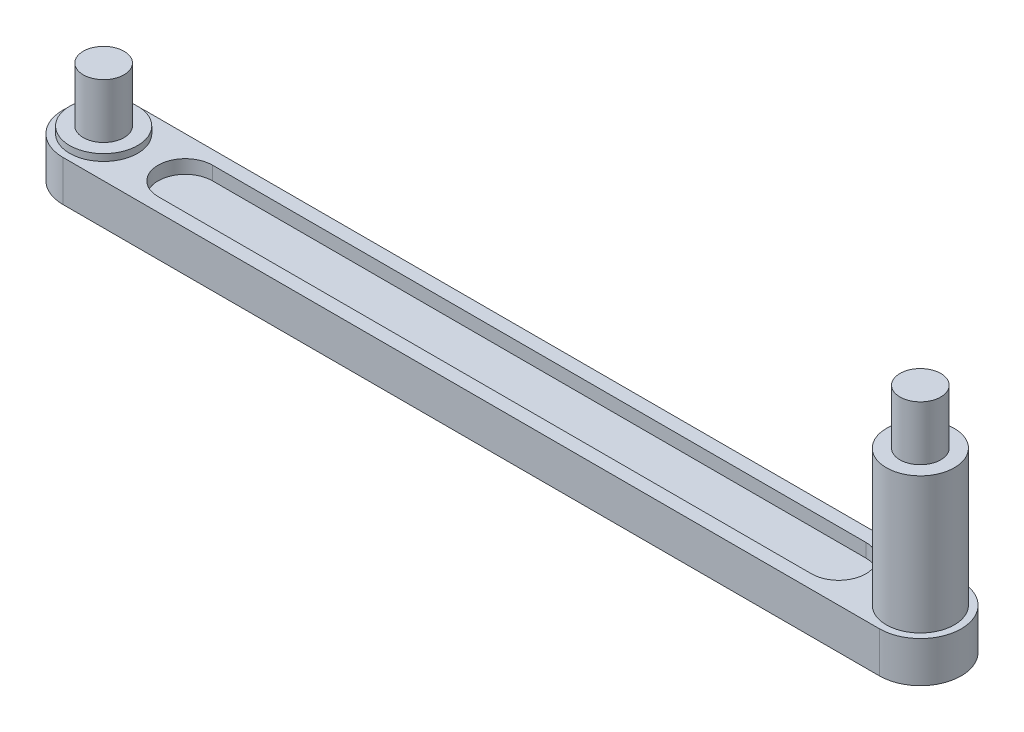
SolidWorks part; units mm, degrees
material "ABS"
ref_plane "Спереди" through (0, 0, 0) normal (0, 0, 1) x (1, 0, 0)
ref_plane "Сверху" through (0, 0, 0) normal (0, 1, 0) x (1, 0, 0)
ref_plane "Справа" through (0, 0, 0) normal (1, 0, 0) x (0, 0, -1)
sketch "Эскиз1" plane through (0, 0, 0) normal (0, 1, 0) x (1, 0, 0)
  line L0 (30, 0) -> (-30, 0) construction
  line L1 (30, -3) -> (-30, -3)
  line L2 (30, 3) -> (-30, 3)
  arc A0 (30, -3) -> (30, 3) centre (30, 0) ccw
  arc A1 (-30, 3) -> (-30, -3) centre (-30, 0) ccw
  circle A2 centre (-30, 0) radius 2.5 construction
  point P2 (0, 0)
  dimension "D2" = 5
  dimension "D3" = 0.5
  dimension "D1" = 60
extrude "Бобышка-Вытянуть1" add sketch "Эскиз1" along normal blind 3
sketch "Эскиз2" plane through (0, 3, 0) normal (0, 1, 0) x (1, 0, 0)
  circle A0 centre (-30, 0) radius 2.5
  circle A1 centre (30, 0) radius 2.5
  arc M1 (30, -3) -> (30, 3) centre (30, 0) ccw
  arc M3 (-30, 3) -> (-30, -3) centre (-30, 0) ccw
extrude "Бобышка-Вытянуть2" add sketch "Эскиз2" along normal blind 0.5 contours A0 M3 region at (-30, 3, 0)
sketch "Эскиз3" plane through (0, 3, 0) normal (0, 1, 0) x (1, 0, 0)
  circle A0 centre (-30, 0) radius 1.5
  circle A1 centre (30, 0) radius 1.5
  dimension "D2" = 3
extrude "Бобышка-Вытянуть3" add sketch "Эскиз3" along normal offset from surface (4.5 mm away) 4 contours A0 region at (-30, 3, 0) up to face at (-30, 3.5, 2.5) offset beyond the face yes
extrude "Бобышка-Вытянуть4" add sketch "Эскиз2<3>" along normal blind 10 contours A1 M1 region at (30, 3, 0)
sketch "Эскиз2<3>" plane through (0, 3, 0) normal (0, 1, 0) x (1, 0, 0) same geometry as "Эскиз2"
extrude "Бобышка-Вытянуть5" add sketch "Эскиз3<3>" along normal offset from surface (14 mm away) 4 contours A1 region at (30, 3, 0) up to face at (30, 13, 2.5) offset beyond the face yes
sketch "Эскиз3<3>" plane through (0, 3, 0) normal (0, 1, 0) x (1, 0, 0) same geometry as "Эскиз3"
sketch "Эскиз4" plane through (0, 3, 0) normal (0, 1, 0) x (1, 0, 0)
  line L0 (24, 0) -> (-24, 0) construction
  line L1 (24, -2) -> (-24, -2)
  line L2 (24, 2) -> (-24, 2)
  line L3 (-24, 2) -> (-24, 3) construction
  line L4 (30, 3) -> (-30, 3) construction
  line L6 (-26, 0) -> (-27, 0) construction
  arc A0 (24, -2) -> (24, 2) centre (24, 0) ccw
  arc A1 (-24, 2) -> (-24, -2) centre (-24, 0) ccw
  arc A2 (-30, 3) -> (-30, -3) centre (-30, 0) ccw construction
  point P2 (0, 0)
  dimension "D1" = 1
extrude "Вырез-Вытянуть1" cut sketch "Эскиз4" against normal offset from surface (1 mm away) 2 up to face at (0, 0, 0)
